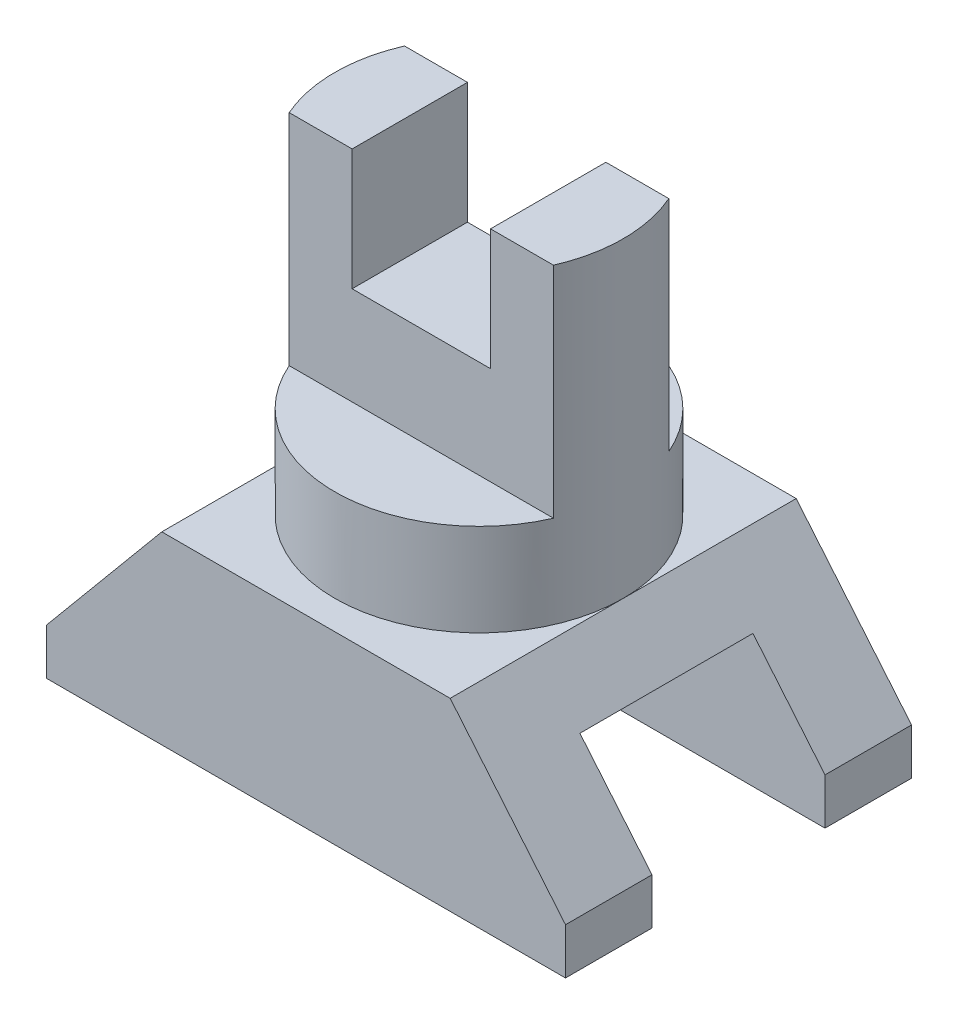
SolidWorks part; units mm, degrees
ref_plane "Front Plane" through (0, 0, 0) normal (0, 0, 1) x (1, 0, 0)
ref_plane "Top Plane" through (0, 0, 0) normal (0, 1, 0) x (1, 0, 0)
ref_plane "Right Plane" through (0, 0, 0) normal (1, 0, 0) x (0, 0, -1)
sketch "Sketch1" plane through (0, 0, 0) normal (0, 0, 1) x (1, 0, 0)
  line L0 (-55.4325, -19.0427) -> (-55.4325, -27.0427)
  line L1 (-55.4325, -27.0427) -> (34.5675, -27.0427)
  line L2 (34.5675, -27.0427) -> (34.5675, -19.0427)
  line L5 (-35.4325, 4.9573) -> (14.5675, 4.9573)
  line L6 (14.5675, 4.9573) -> (34.5675, -19.0427)
  line L7 (-35.4325, 4.9573) -> (-55.4325, -19.0427)
extrude "Boss-Extrude1" add sketch "Sketch1" along normal blind 60
sketch "Sketch2" plane through (0, 4.9573, 0) normal (0, 1, 0) x (1, 0, 0)
  line L3 (-35.4325, -60) -> (-35.4325, 0) construction
  line L4 (14.5675, -60) -> (-35.4325, -60) construction
  circle A0 centre (-10.4325, -30) radius 25
  point P6 (-11.5172, -54.9875)
  dimension "D1" = 25
  dimension "D2" = 30
extrude "Boss-Extrude2" add sketch "Sketch2" along normal blind 16
sketch "Sketch3" plane through (0, 20.9573, 0) normal (0, 1, 0) x (1, 0, 0)
  line L1 (-10.4325, -20) -> (-33.3454, -20)
  line L2 (-22.4325, -40) -> (-22.4325, -20)
  line L3 (-10.4325, -40) -> (-33.3454, -40)
  line L4 (-10.4325, -20) -> (12.4804, -20)
  line L5 (-10.4325, -40) -> (12.4804, -40)
  line L7 (1.5675, -40) -> (1.5675, -20)
  arc A0 (14.5675, -30) -> (-35.4325, -30) centre (-10.4325, -30) ccw construction
  arc A1 (-35.4325, -30) -> (14.5675, -30) centre (-10.4325, -30) ccw construction
  circle A2 centre (-10.4325, -30) radius 25 construction
  arc A4 (12.4804, -40) -> (12.4804, -20) centre (-10.4325, -30) ccw
  arc A5 (-33.3454, -20) -> (-33.3454, -40) centre (-10.4325, -30) ccw
  circle M9 centre (-10.4325, -30) radius 25
extrude "Boss-Extrude4" add sketch "Sketch3" along normal blind 17 contours L5 L7 L4 L1 L2 L3 region at (-10.4325, 20.9573, 30)
extrude "Boss-Extrude5" add sketch "Sketch3<4>" along normal blind 38 contours L3 L2 L1 M9 | L7 L5 L4 M9 region at (-28.6062, 20.9573, 30) region at (7.7412, 20.9573, 30)
sketch "Sketch3<4>" plane through (0, 20.9573, 0) normal (0, 1, 0) x (1, 0, 0) same geometry as "Sketch3"
sketch "Sketch4" plane through (34.5675, 0, 0) normal (1, 0, 0) x (0, 0, -1)
  line L0 (-60, -27.0427) -> (0, -27.0427) construction
  line L1 (-45, -27.0427) -> (-15, -27.0427)
  line L2 (-45, -27.0427) -> (-45, -4.0427)
  line L3 (-45, -4.0427) -> (-15, -4.0427)
  line L4 (-15, -27.0427) -> (-15, -4.0427)
  line L5 (-60, -27.0427) -> (-60, -19.0427) construction
  line L6 (0, -27.0427) -> (0, -19.0427) construction
  dimension "D1" = 15
  dimension "D2" = 15
  dimension "D3" = 23
extrude "Cut-Extrude1" cut sketch "Sketch4" against normal blind 110
